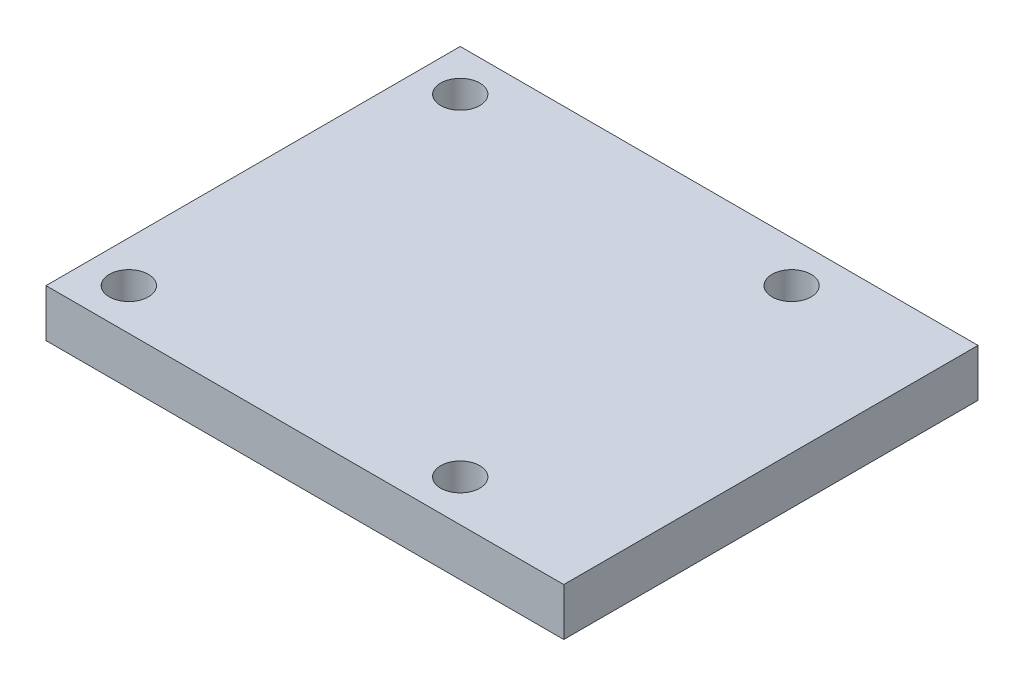
SolidWorks part; units mm, degrees
ref_plane "Front Plane" through (0, 0, 0) normal (0, 0, 1) x (1, 0, 0)
ref_plane "Top Plane" through (0, 0, 0) normal (0, 1, 0) x (1, 0, 0)
ref_plane "Right Plane" through (0, 0, 0) normal (1, 0, 0) x (0, 0, -1)
sketch "Sketch1" plane through (0, 0, 0) normal (0, 1, 0) x (1, 0, 0)
  line L1 (-15.875, -12.7) -> (15.875, -12.7)
  line L2 (-15.875, -12.7) -> (-15.875, 12.7)
  line L3 (-15.875, 12.7) -> (15.875, 12.7)
  line L4 (15.875, -12.7) -> (15.875, 12.7)
  line L5 (-15.875, -12.7) -> (15.875, 12.7) construction
  line L6 (-15.875, 12.7) -> (15.875, -12.7) construction
  point P0 (0, 0)
  dimension "D1" = 31.75
  dimension "D2" = 25.4
extrude "Boss-Extrude1" add sketch "Sketch1" along normal blind 2.921
sketch "Sketch2" plane through (0, 2.921, 0) normal (0, 1, 0) x (1, 0, 0)
  line L2 (15.875, 12.7) -> (-15.875, 12.7) construction
  line L3 (-15.875, 12.7) -> (-15.875, -12.7) construction
  line L4 (-15.875, -12.7) -> (15.875, -12.7) construction
  point P4 (6.985, 10.16)
  point P5 (6.985, -10.16)
  point P6 (-13.335, -10.16)
  point P7 (-13.335, 10.16)
  dimension "D1" = 2.54
  dimension "D2" = 2.54
  dimension "D3" = 2.54
  dimension "D4" = 2.54
  dimension "D5" = 22.86
hole_wizard "M2 Clearance Hole1" positions "Sketch3" profile "Sketch4" hole size "M2" standard "ANSI Metric" end condition through all
sketch "Sketch3" plane through (0, 2.921, 0) normal (0, 1, 0) x (1, 0, 0)
  point P0 (-13.335, 10.16)
  point P3 (6.985, 10.16)
  point P6 (6.985, -10.16)
  point P9 (-13.335, -10.16)
sketch "Sketch4" plane through (-13.335, 2.921, -10.16) normal (1, 0, 0) x (0, 0, 1)
  line L0 (0, 0) -> (0, 2.921)
  line L1 (0, 2.921) -> (1.2, 2.921)
  line L2 (1.2, 2.921) -> (1.2, 0)
  line L5 (1.2, 0) -> (0, 0)
  line L11 (0, -6.35) -> (0, 107.95) construction
  dimension "Thru Hole Dia." = 2.4
  dimension "Thru Hole Depth" = 2.921
